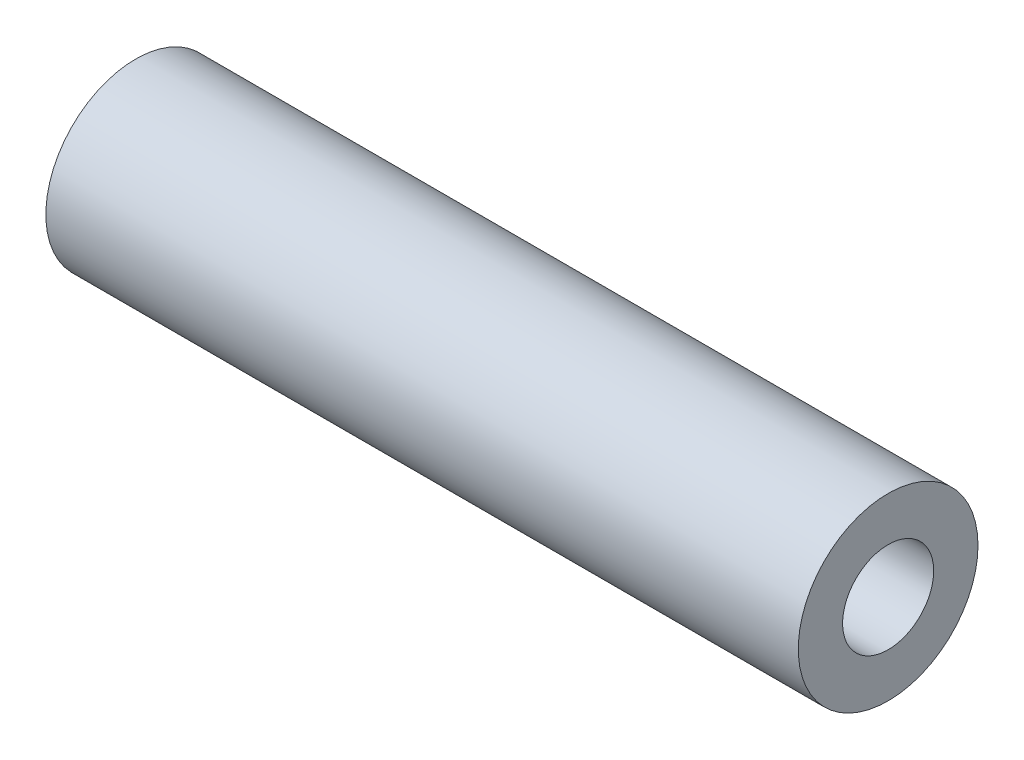
SolidWorks part; units mm, degrees
material "6061-T6 (SS)"
ref_plane "Front" through (0, 0, 0) normal (0, 0, 1) x (1, 0, 0)
ref_plane "Top" through (0, 0, 0) normal (0, 1, 0) x (1, 0, 0)
ref_plane "Right" through (0, 0, 0) normal (1, 0, 0) x (0, 0, -1)
sketch "Sketch1" plane through (0, 0, 0) normal (1, 0, 0) x (0, 0, -1)
  circle A0 centre (0, 0) radius 2.413
  circle A1 centre (0, 0) radius 4.7625
  dimension "D1" = 4.826
  dimension "D2" = 9.525
extrude "Boss-Extrude1" add sketch "Sketch1" along normal mid plane 39.878
